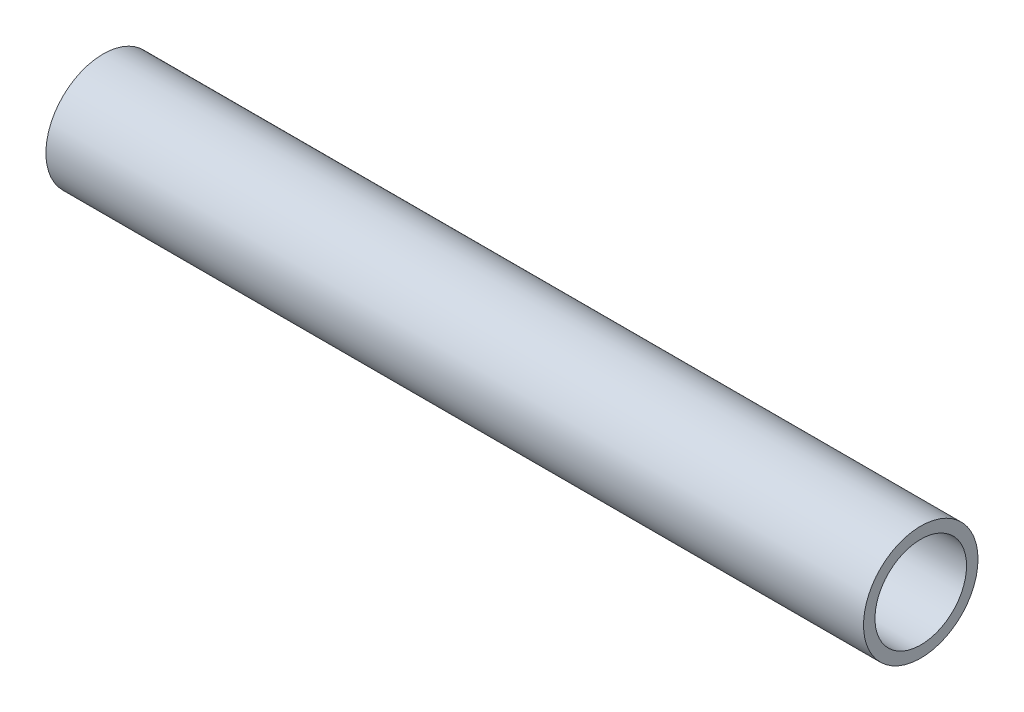
SolidWorks part; units mm, degrees
material "PC High Viscosity"
ref_plane "Front Plane" through (0, 0, 0) normal (0, 0, 1) x (1, 0, 0)
ref_plane "Top Plane" through (0, 0, 0) normal (0, 1, 0) x (1, 0, 0)
ref_plane "Right Plane" through (0, 0, 0) normal (1, 0, 0) x (0, 0, -1)
sketch "Sketch1" plane through (0, 0, 0) normal (1, 0, 0) x (0, 0, -1)
  circle A0 centre (0, 0) radius 15.875
  dimension "D1" = 31.75
extrude "Extrude-Thin1" add sketch "Sketch1" along normal mid plane 226.7615 thin thin type one direction reverse wall 3.175
